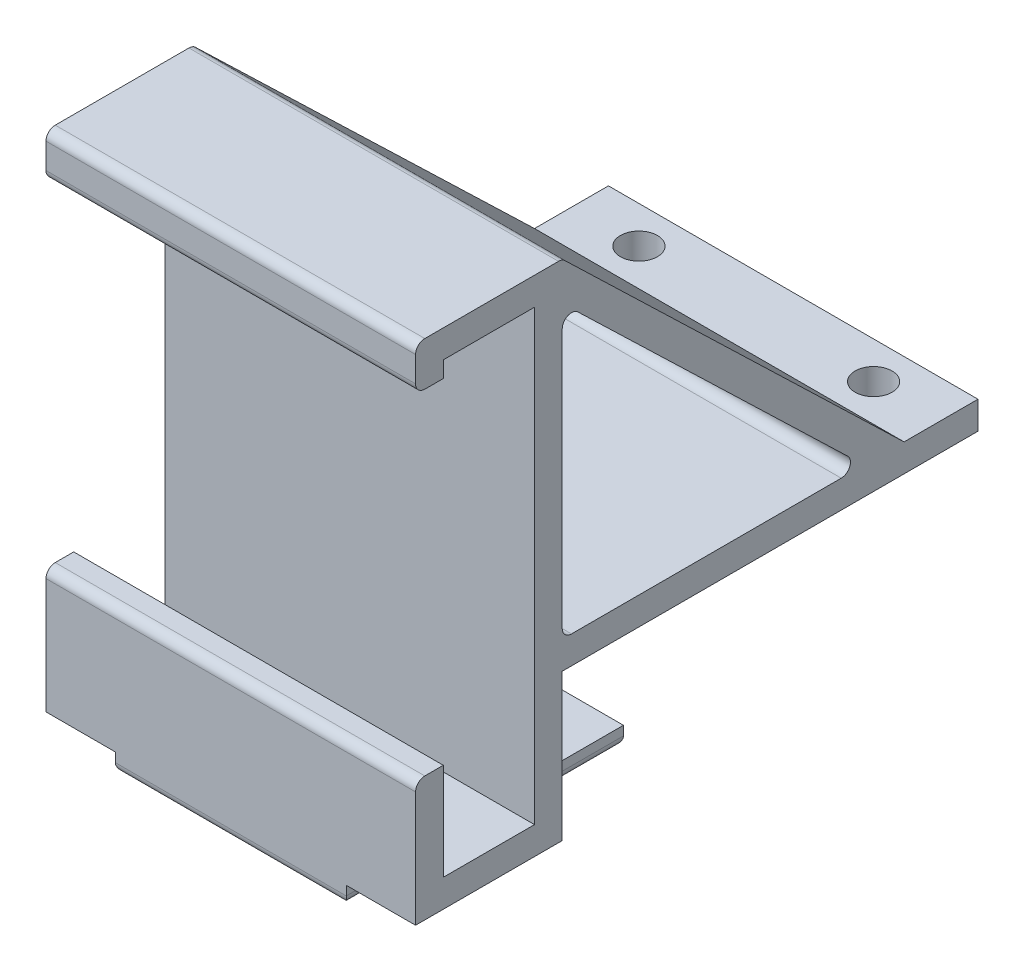
SolidWorks part; units mm, degrees
ref_plane "Front Plane" through (0, 0, 0) normal (0, 0, 1) x (1, 0, 0)
ref_plane "Top Plane" through (0, 0, 0) normal (0, 1, 0) x (1, 0, 0)
ref_plane "Right Plane" through (0, 0, 0) normal (1, 0, 0) x (0, 0, -1)
sketch "Sketch1" plane through (0, 0, 0) normal (0, 0, 1) x (1, 0, 0)
  line L0 (0, 20) -> (0, 0) construction
  line L1 (-18, 18) -> (18, 18)
  line L2 (-18, 18) -> (-18, -18)
  line L3 (-18, -18) -> (18, -18)
  line L4 (18, 18) -> (18, -18)
  line L5 (-18, 18) -> (18, -18) construction
  line L6 (-18, -18) -> (18, 18) construction
  line L7 (-20, 20) -> (20, 20)
  line L8 (-20, 20) -> (-20, -28.5)
  line L9 (-20, -28.5) -> (20, -28.5)
  line L10 (20, 20) -> (20, -28.5)
  point P0 (0, 0)
  dimension "D1" = 36
  dimension "D2" = 40
  dimension "D3" = 48.5
  dimension "D4" = 2
extrude "Boss-Extrude1" add sketch "Sketch1" along normal blind 13.5 contours L2 L3 L4 L1
extrude "Boss-Extrude2" add sketch "Sketch1<3>" against normal blind 10 separate body contours L10 L7 L8 L9 L1 L4 L3 L2 | L4 L1 L2 L3 region at (0, 0, 0) region at (0, 19.3713, 0)
sketch "Sketch1<3>" plane through (0, 0, 0) normal (0, 0, 1) x (1, 0, 0) same geometry as "Sketch1"
fillet "Fillet1" radius 3.5 4 edges at (20, 20, -5) (-20, -28.5, -5) (20, -28.5, -5) (-20, 20, -5)
fillet "Fillet2" radius 3.5 4 edges at (18, 18, 6.75) (18, -18, 6.75) (-18, -18, 6.75) (-18, 18, 6.75)
fillet "Fillet3" radius 1 8 edges at (-18.9749, 18.9749, 0) (0, 20, 0) (18.9749, 18.9749, 0) (20, -4.25, 0) (18.9749, -27.4749, 0) (0, -28.5, 0) (-18.9749, -27.4749, 0) (-20, -4.25, 0)
fillet "Fillet4" radius 1 8 edges at (-18.9749, 18.9749, -10) (-20, -4.25, -10) (-18.9749, -27.4749, -10) (0, -28.5, -10) (18.9749, -27.4749, -10) (20, -4.25, -10) (18.9749, 18.9749, -10) (0, 20, -10)
fillet "Fillet5" radius 1 8 edges at (-16.9749, 16.9749, 13.5) (0, 18, 13.5) (16.9749, 16.9749, 13.5) (18, 0, 13.5) (16.9749, -16.9749, 13.5) (0, -18, 13.5) (-16.9749, -16.9749, 13.5) (-18, 0, 13.5)
sketch "Sketch2" plane through (0, 0, 0) normal (1, 0, 0) x (0, 0, -1)
  line L0 (-2.875, -18) -> (-2.875, -31.5)
  line L1 (0, -18) -> (-12.5, -18) construction
  line L2 (-2.875, -31.5) -> (13, -31.5)
  line L3 (13, -31.5) -> (13, 20)
  line L4 (-2.875, -18) -> (0.125, -18)
  line L6 (0.125, -18) -> (0.125, -28.5)
  line L7 (0.125, -28.5) -> (10, -28.5)
  line L8 (10, -28.5) -> (10, 20)
  line L10 (9, -28.5) -> (1, -28.5) construction
  line L11 (10, 16.5) -> (10, 19) construction
  line L12 (0, -18) -> (0, -14.5) construction
  line L13 (0.125, -28.5) -> (0.125, -31.5) construction
  line L14 (10, -28.5) -> (13, -28.5) construction
  line L16 (13, 20) -> (13, 23)
  line L17 (13, 23) -> (-2.875, 23)
  line L18 (-2.875, 23) -> (-2.875, 18.25)
  line L19 (-2.875, 18.25) -> (0.125, 18.25)
  line L21 (0.125, 18.25) -> (0.125, 20)
  line L22 (0.125, 20) -> (10, 20)
  line L24 (10, 20) -> (10, 23) construction
  line L25 (1, 20) -> (9, 20) construction
  line L26 (-12.5, 18) -> (0, 18) construction
  line L27 (0.125, 20) -> (-2.875, 20) construction
  dimension "D1" = 0.125
  dimension "D2" = 3
  dimension "D3" = 0.25
extrude "Boss-Extrude3" add sketch "Sketch2" along normal up to surface and the other way up to surface separate body up to face at (20, -4.25, -5) other way up to face at (-20, -4.25, -5)
sketch "Sketch3" plane through (0, 0, 0) normal (1, 0, 0) x (0, 0, -1)
  line L1 (58, -15.625) -> (10, -15.625)
  line L2 (50, -12.625) -> (58, -12.625)
  line L3 (10, 23) -> (10, -15.625)
  line L4 (13, 18.8354) -> (13, -12.625)
  line L5 (13, -12.625) -> (45.6747, -12.625)
  line L6 (45.6747, -12.625) -> (13, 18.8354)
  line L7 (10, -28.5) -> (10, 20) construction
  line L8 (58, -12.625) -> (58, -15.625)
  line L9 (10, 23) -> (13, 23)
  line L10 (13, 23) -> (50, -12.625)
  line L11 (45.6747, -12.625) -> (50, -12.625) construction
  dimension "D1" = 15.875
  dimension "D2" = 48
  dimension "D3" = 3
  dimension "D4" = 3
  dimension "D5" = 3
  dimension "D6" = 8
extrude "Boss-Extrude4" add sketch "Sketch3" along normal up to surface and the other way up to surface up to face at (20, -2.7917, -2.9167) other way up to face at (-20, -2.7917, -2.9167)
sketch "Sketch8" plane through (0, 0, 0) normal (1, 0, 0) x (0, 0, -1)
  line L0 (-2.875, -31.5) -> (-2.875, -33.5)
  line L1 (-2.875, -33.5) -> (27.125, -33.5)
  line L2 (27.125, -33.5) -> (27.125, -31.5)
  line L3 (27.125, -31.5) -> (13, -31.5)
  line L20 (50, -12.625) -> (13, 23)
  line L21 (13, 23) -> (-2.875, 23)
  line L22 (-2.875, 23) -> (-2.875, 18.25)
  line L23 (-2.875, 18.25) -> (0.125, 18.25)
  line L24 (0.125, 18.25) -> (0.125, 20)
  line L25 (0.125, 20) -> (10, 20)
  line L26 (10, 20) -> (10, -28.5)
  line L27 (10, -28.5) -> (0.125, -28.5)
  line L28 (0.125, -28.5) -> (0.125, -18)
  line L29 (0.125, -18) -> (-2.875, -18)
  line L30 (-2.875, -18) -> (-2.875, -31.5)
  line L31 (-2.875, -31.5) -> (13, -31.5)
  line L32 (13, -31.5) -> (13, -15.625)
  line L33 (13, -15.625) -> (58, -15.625)
  line L34 (58, -15.625) -> (58, -12.625)
  line L35 (58, -12.625) -> (50, -12.625)
  line L47 (-2.875, -31.5) -> (13, -31.5)
  dimension "D1" = 30
  dimension "D2" = 0
  dimension "D3" = 2
extrude "Boss-Extrude5" add sketch "Sketch8" along normal mid plane 25
sketch "Sketch9" plane through (0, -12.625, 0) normal (0, 1, 0) x (1, 0, 0)
  line L0 (12.7, 54) -> (20, 54) construction
  line L1 (20, 50) -> (20, 58) construction
  line L2 (0, 58) -> (0, 50) construction
  line L3 (20, 58) -> (-20, 58) construction
  line L4 (20, 50) -> (-20, 50) construction
  circle A0 centre (12.7, 54) radius 2
  circle A1 centre (-12.7, 54) radius 2
  dimension "D1" = 4
  dimension "D2" = 7.3
extrude "Cut-Extrude3" cut sketch "Sketch9" against normal through all
delete or keep bodies "Body-Delete/Keep 1" type keep bodies bodies 108
fillet "Fillet6" radius 1 7 edges at (0, -12.625, -45.6747) (0, -12.625, -13) (0, 18.8354, -13) (0, -18, 2.875) (0, 18.25, 2.875) (0, 23, 2.875) (0, 23, -13)
fillet "Fillet7" radius 1 4 edges at (0, -33.5, 2.875) (12.5, -33.5, -12.125) (0, -33.5, -27.125) (-12.5, -33.5, -12.125)
